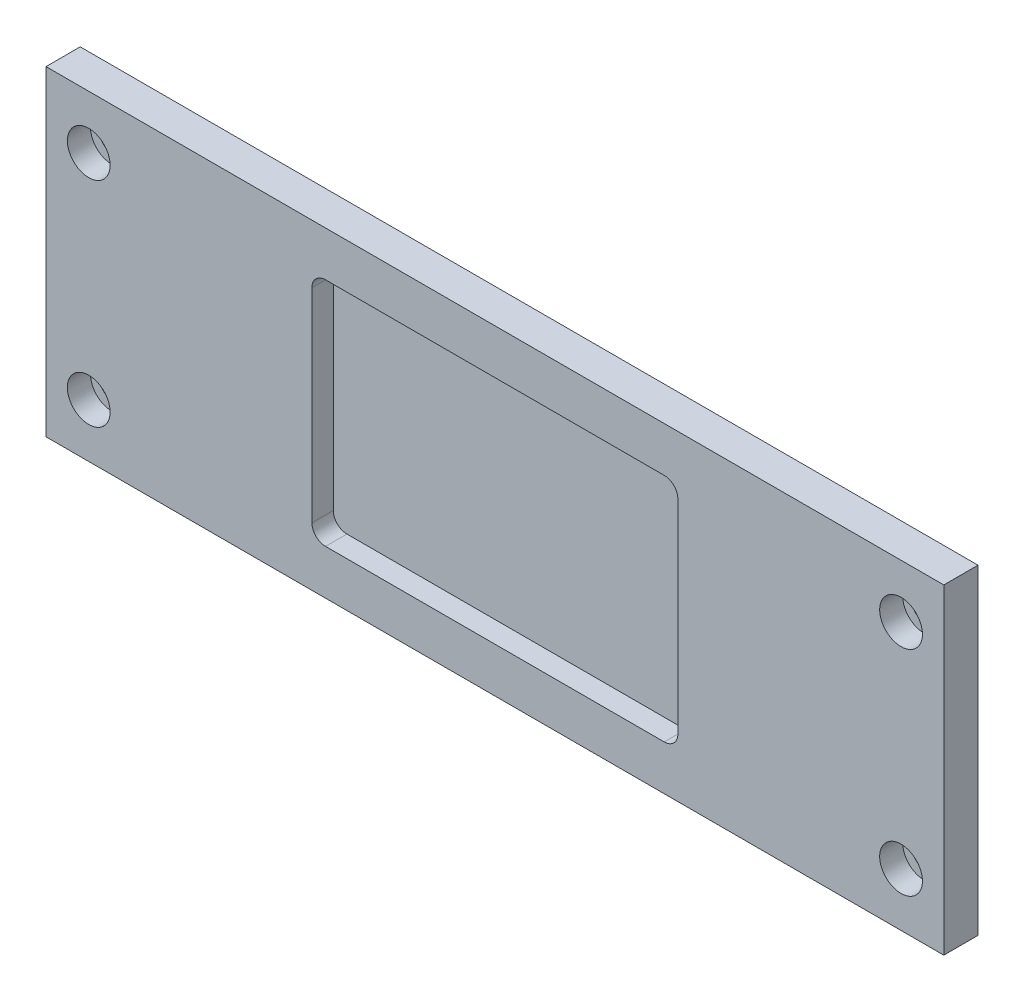
SolidWorks part; units mm, degrees
ref_plane "前视基准面" through (0, 0, 0) normal (0, 0, 1) x (1, 0, 0)
ref_plane "上视基准面" through (0, 0, 0) normal (0, 1, 0) x (1, 0, 0)
ref_plane "右视基准面" through (0, 0, 0) normal (1, 0, 0) x (0, 0, -1)
sketch "草图1" plane through (0, 0, 0) normal (0, 0, 1) x (1, 0, 0)
  line L1 (0, 0) -> (210, 0)
  line L2 (0, 0) -> (0, 75)
  line L3 (0, 75) -> (210, 75)
  line L4 (210, 0) -> (210, 75)
  dimension "D1" = 210
  dimension "D2" = 75
extrude "凸台-拉伸1" add sketch "草图1" along normal blind 8
sketch "草图2" plane through (0, 0, 8) normal (0, 0, 1) x (1, 0, 0)
  line L0 (210, 37.5) -> (0, 37.5) construction
  line L1 (210, 0) -> (210, 75) construction
  line L2 (0, 75) -> (0, 0) construction
  line L3 (0, 37.5) -> (105, 37.5) construction
  line L4 (105, 37.5) -> (105, -2.643) construction
  line L6 (144.62, 64.5) -> (65.38, 64.5)
  line L7 (147.8, 61.32) -> (147.8, 13.68)
  line L8 (144.62, 10.5) -> (65.38, 10.5)
  line L9 (62.2, 61.32) -> (62.2, 13.68)
  arc A0 (65.38, 10.5) -> (62.2, 13.68) centre (65.38, 13.68) cw
  arc A1 (62.2, 61.32) -> (65.38, 64.5) centre (65.38, 61.32) cw
  arc A2 (144.62, 10.5) -> (147.8, 13.68) centre (144.62, 13.68) ccw
  arc A3 (144.62, 64.5) -> (147.8, 61.32) centre (144.62, 61.32) cw
  point P16 (62.2, 64.5)
  point P19 (147.8, 10.5)
  point P22 (147.8, 64.5)
  dimension "D3" = 3.18
  dimension "D1" = 54
  dimension "D2" = 85.6
extrude "切除-拉伸1" cut sketch "草图2" against normal blind 5
hole_wizard "M5 六角凹头螺钉的柱形沉头孔1" positions "草图3" profile "草图4" counterbore size "M5" standard "ISO"
sketch "草图3" plane through (0, 0, 8) normal (0, 0, 1) x (1, 0, 0)
  line L0 (0, 37.5) -> (210, 37.5) construction
  line L1 (0, 75) -> (0, 0) construction
  line L2 (210, 0) -> (210, 75) construction
  line L3 (210, 37.5) -> (105, 37.5) construction
  line L4 (105, 37.5) -> (105, -47.7536) construction
  point P0 (10, 62.5)
  point P4 (10, 12.5)
  point P18 (200, 62.5)
  point P19 (200, 12.5)
  dimension "D1" = 50
  dimension "D2" = 10
sketch "草图4" plane through (10, 62.5, 8) normal (1, 0, 0) x (0, -1, 0)
  line L0 (0, 0) -> (0, 11.7524)
  line L1 (0, 11.7524) -> (2.75, 10.1)
  line L2 (2.75, 10.1) -> (2.75, 5.4)
  line L3 (2.75, 5.4) -> (5, 5.4)
  line L4 (5, 5.4) -> (5, 0)
  line L5 (5, 0) -> (0, 0)
  line L10 (0, 11.7524) -> (-2.75, 10.1) construction
  line L11 (0, -6.35) -> (0, 107.95) construction
  dimension "孔直径" = 5.5
  dimension "孔深度" = 10.1
  dimension "柱形沉头孔直径" = 10
  dimension "柱形沉头孔深度" = 5.4
  dimension "导头角度" = 118
